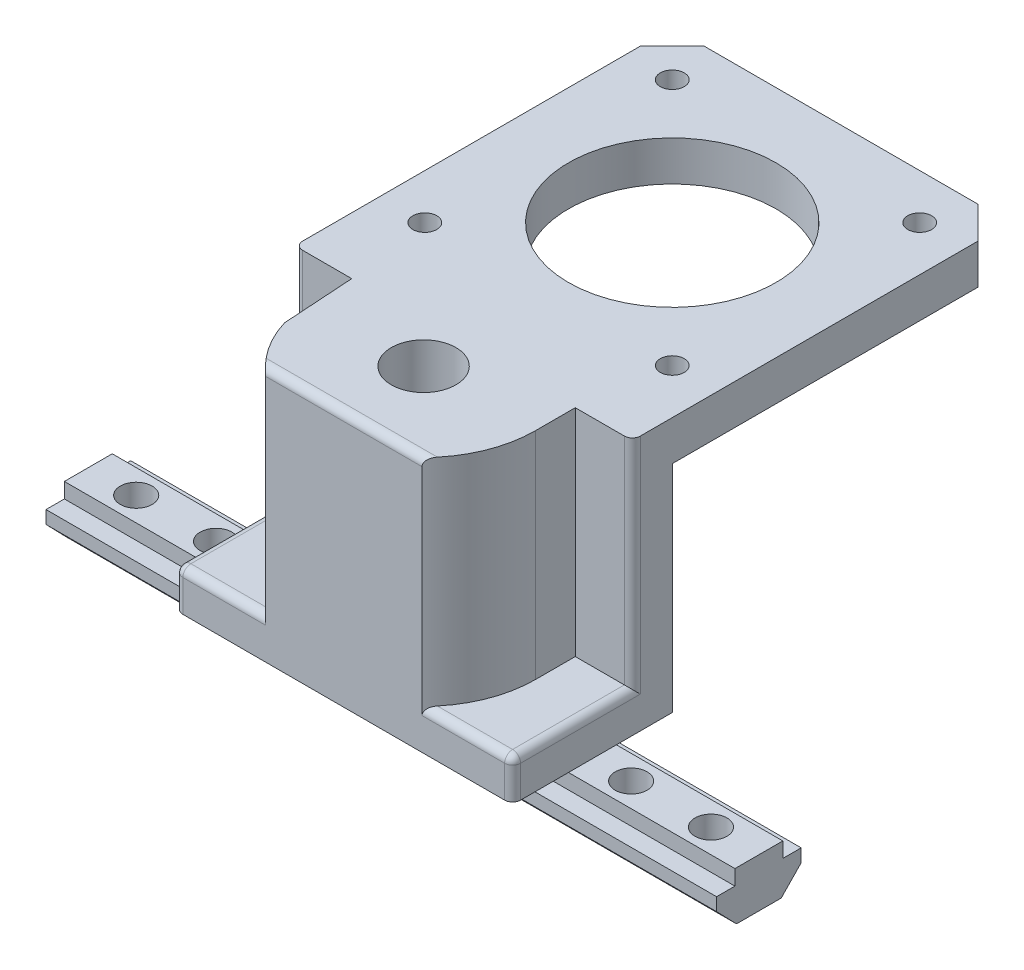
SolidWorks part; units mm, degrees
ref_plane "Front (XY)" through (0, 0, 0) normal (0, 0, 1) x (1, 0, 0)
ref_plane "Top (XZ)" through (0, 0, 0) normal (0, 1, 0) x (1, 0, 0)
ref_plane "Right (YZ)" through (0, 0, 0) normal (1, 0, 0) x (0, 0, -1)
sketch "Sketch1" plane through (0, 0, 0) normal (1, 0, 0) x (0, 0, -1)
  line L0 (0, 0) -> (0, 6.1) construction
  line L1 (-3, 6.1) -> (3, 6.1)
  line L2 (-3, 6.1) -> (-3, 4.2)
  line L3 (3, 6.1) -> (3, 4.2)
  line L4 (-3, 4.2) -> (-5.3, 4.2)
  line L5 (3, 4.2) -> (5.3, 4.2)
  line L6 (-5.3, 4.2) -> (-5.3, 2.58)
  line L7 (5.3, 4.2) -> (5.3, 2.58)
  line L8 (-2.8, 0) -> (2.8, 0)
  line L9 (-2.8, 0) -> (-5.3, 2.58)
  line L10 (2.8, 0) -> (5.3, 2.58)
  point P4 (0, 6.1)
  point P13 (0, 0)
  dimension "D1" = 6
  dimension "D2" = 1.9
  dimension "D3" = 2.3
  dimension "D4" = 1.62
  dimension "D5" = 6.1
  dimension "D6" = 5.6
extrude "Boss-Extrude1" add sketch "Sketch1" along normal mid plane 84
ref_plane "Plane1" through (0, 6.1, 0) normal (0, 1, 0) x (1, 0, 0)
sketch "Sketch2" plane through (0, 6.1, 0) normal (0, 1, 0) x (1, 0, 0)
  line L4 (21.15, -10) -> (21.15, 10)
  line L5 (21.15, 10) -> (-21.15, 10)
  line L6 (-21.15, -10) -> (21.15, -10)
  line L7 (-21.15, -10) -> (-21.15, 10)
  point P1 (-21.15, 0)
  point P8 (21.15, 0)
  dimension "D1" = 42.3
  dimension "D2" = 20
  dimension "D3" = 21.15
extrude "Boss-Extrude2" add sketch "Sketch2" along normal blind 32
ref_plane "Plane2" through (0, 33.1, 0) normal (0, 1, 0) x (1, 0, 0)
sketch "Sketch3" plane through (0, 33.1, 0) normal (0, 1, 0) x (1, 0, 0)
  line L2 (21.15, 10) -> (21.15, 52.3)
  line L3 (21.15, 52.3) -> (-21.15, 52.3)
  line L4 (-21.15, 52.3) -> (-21.15, 10)
  line L5 (-21.15, 10) -> (21.15, 10)
  dimension "D1" = 42.3
  dimension "D2" = 42.3
extrude "Boss-Extrude3" add sketch "Sketch3" along normal blind 5
shell "Shell2" thickness 5 removed face at (-21.15, 20.85, -13.075) removed face at (0, 22.1, 10) removed face at (0, 38.1, -21.15) removed face at (21.15, 20.85, -13.075)
chamfer "Chamfer2" distance 4 angle 45 2 edges at (-21.15, 35.6, -52.3) (21.15, 35.6, -52.3)
sketch "Sketch4" plane through (0, 33.1, 0) normal (0, 1, 0) x (1, 0, 0)
  line L2 (-21.15, 10) -> (21.15, 10) construction
  line L3 (-21.15, 48.3) -> (-21.15, 5) construction
  circle A0 centre (0, 31.15) radius 13
  dimension "D1" = 26
  dimension "D2" = 21.15
  dimension "D3" = 21.15
extrude "Cut-Extrude1" cut sketch "Sketch4" against normal through all both and the other way through all
ref_plane "Plane3" through (0, 38.1, 0) normal (0, 1, 0) x (1, 0, 0)
fillet "Fillet1" radius 1 6 edges at (21.15, 24.6, -5) (-21.15, 24.6, -5) (21.15, 11.1, 2.5) (-21.15, 11.1, 2.5) (-21.15, 8.6, 10) (21.15, 8.6, 10)
sketch "Sketch16" plane through (0, 11.1, 0) normal (0, 1, 0) x (1, 0, 0)
  circle A0 centre (0, 0) radius 4 construction
  dimension "D1" = 8
sketch "Sketch17" plane through (0, 11.1, 0) normal (0, 1, 0) x (1, 0, 0)
  line L0 (20.15, 5) -> (-20.15, 5) construction
  line L1 (14, 5) -> (-14, 5)
  line L2 (0, 0) -> (0, 3.0984) construction
  line L3 (14, 5) -> (14, 0)
  line L4 (-14, 5) -> (-13.4164, -4)
  line L5 (-20.15, -10) -> (20.15, -10) construction
  line L6 (-9.798, -10) -> (9.798, -10)
  arc A0 (9.798, -10) -> (14, 0) centre (0, 0) ccw
  circle A2 centre (0, 0) radius 14
  arc A3 (-13.4164, -4) -> (-9.798, -10) centre (0, 0) ccw
  dimension "D2" = 28
  dimension "D3" = 9
  dimension "D1" = 10
extrude "Boss-Extrude4" add sketch "Sketch17" along normal up to surface (27 mm away) up to face at (0, 38.1, -18.15)
sketch "Sketch18" plane through (0, 11.1, 0) normal (0, 1, 0) x (1, 0, 0)
  circle A0 centre (0, 0) radius 4.05
  dimension "D1" = 8.1
extrude "Cut-Extrude2" cut sketch "Sketch18" along normal through all
fillet "Fillet8" radius 1 5 edges at (0, 38.1, 10) (20.8571, 10.8071, 9.7071) (-20.8571, 10.8071, 9.7071) (14.974, 11.1, 10) (-14.974, 11.1, 10)
sketch "Sketch19" plane through (0, 38.1, 0) normal (0, 1, 0) x (1, 0, 0)
  line L0 (17.15, 52.3) -> (-17.15, 52.3) construction
  line L1 (-21.15, 48.3) -> (-21.15, 6) construction
  circle A0 centre (-15.5, 46.65) radius 1.5
  circle A1 centre (15.5, 46.65) radius 1.5
  circle A2 centre (15.5, 15.65) radius 1.5
  circle A3 centre (-15.5, 15.65) radius 1.5
  dimension "D1" = 3
  dimension "D2" = 5.65
  dimension "D3" = 5.65
  dimension "D4" = 31
  dimension "D5" = 31
extrude "Cut-Extrude3" cut sketch "Sketch19" against normal through all
sketch "Sketch20" plane through (0, 6.1, 0) normal (0, 1, 0) x (1, 0, 0)
  circle A0 centre (36, 0) radius 2
  circle A1 centre (26, 0) radius 2
  circle A2 centre (-26, 0) radius 2
  circle A3 centre (-36, 0) radius 2
  dimension "D1" = 4
  dimension "D2" = 26
  dimension "D3" = 26
  dimension "D4" = 10
  dimension "D5" = 10
extrude "Cut-Extrude4" cut sketch "Sketch20" against normal through all
